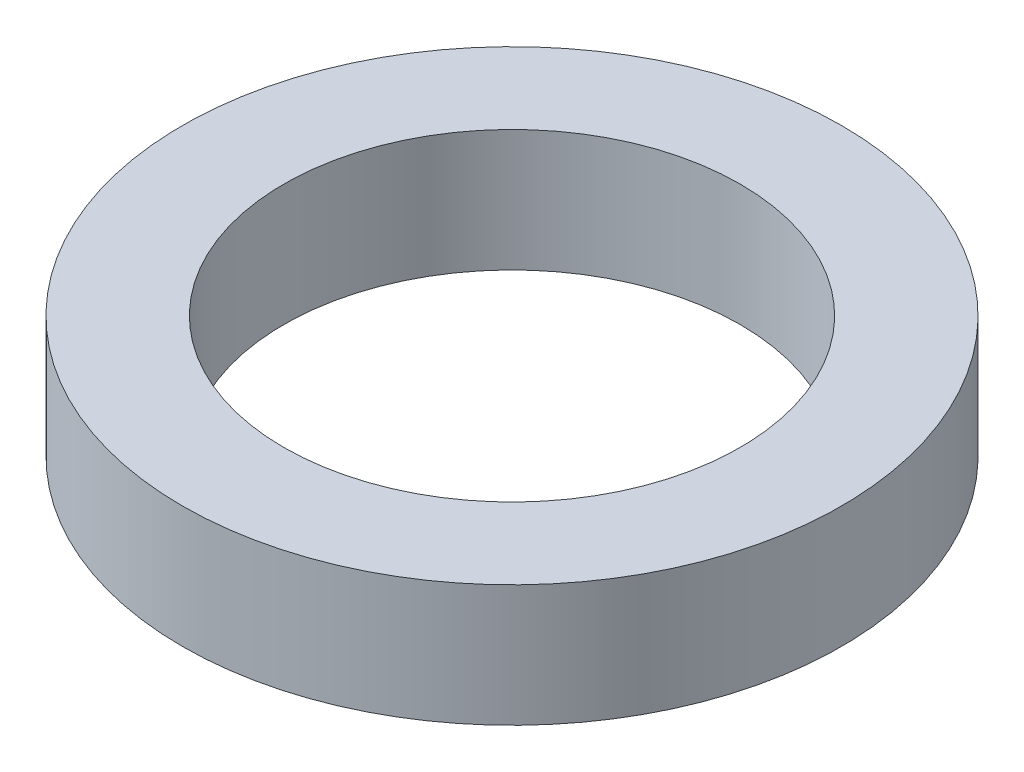
SolidWorks part; units mm, degrees
ref_plane "Front Plane" through (0, 0, 0) normal (0, 0, 1) x (1, 0, 0)
ref_plane "Top Plane" through (0, 0, 0) normal (0, 1, 0) x (1, 0, 0)
ref_plane "Right Plane" through (0, 0, 0) normal (1, 0, 0) x (0, 0, -1)
sketch "Sketch1" plane through (0, 0, 0) normal (0, 1, 0) x (1, 0, 0)
  circle A0 centre (0, 0) radius 32.5
  dimension "FLANGE_OD" = 65
extrude "Boss-Extrude1" add sketch "Sketch1" along normal blind 12
sketch "Sketch2" plane through (0, 0, 0) normal (0, 1, 0) x (1, 0, 0)
  circle A0 centre (0, 0) radius 22.5
  dimension "BORE_D" = 45
extrude "Cut-Extrude1" cut sketch "Sketch2" along normal through all
sketch "Sketch3" plane through (0, 12, 0) normal (0, 1, 0) x (1, 0, 0)
  circle A0 centre (0, 0) radius 13.1539 construction
  circle A1 centre (-13.1539, 0) radius 1.5905
  dimension "BOLT_D" = 3.181
  dimension "BOLT_PCD" = 26.3078
extrude "Cut-Extrude2" cut sketch "Sketch3" against normal blind 10.5545 rebuild error yes
pattern_circular "CirPattern1" count 8 over 360 rebuild error yes
